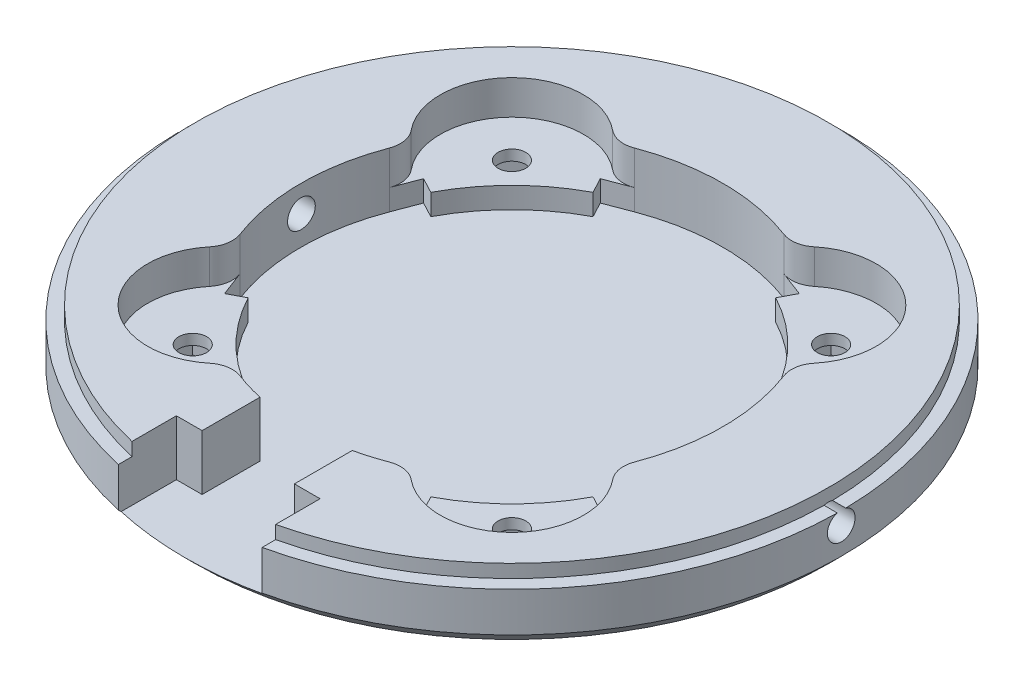
SolidWorks part; units mm, degrees
ref_plane "Front Plane" through (0, 0, 0) normal (0, 0, 1) x (1, 0, 0)
ref_plane "Top Plane" through (0, 0, 0) normal (0, 1, 0) x (1, 0, 0)
ref_plane "Right Plane" through (0, 0, 0) normal (1, 0, 0) x (0, 0, -1)
sketch "Sketch1" plane through (0, 0, 0) normal (0, 1, 0) x (1, 0, 0)
  line L0 (-15.7, 0) -> (15.7, 0) construction
  line L1 (0, 0) -> (12.1057, 12.1057) construction
  line L2 (5.6659, 14.9632) -> (7.5483, 14.2504)
  line L3 (7.5483, 14.2504) -> (6.9276, 13.0786)
  line L4 (14.9632, 5.6659) -> (14.2504, 7.5483)
  line L5 (14.2504, 7.5483) -> (13.0786, 6.9276)
  line L6 (14.9632, -5.6659) -> (14.2504, -7.5483)
  line L7 (14.2504, -7.5483) -> (13.0786, -6.9276)
  line L8 (7.5483, -14.2504) -> (6.9276, -13.0786)
  line L9 (5.6659, -14.9632) -> (7.5483, -14.2504)
  line L10 (-5.6659, -14.9632) -> (-7.5483, -14.2504)
  line L11 (-7.5483, -14.2504) -> (-6.9276, -13.0786)
  line L12 (-14.2504, -7.5483) -> (-13.0786, -6.9276)
  line L13 (-14.9632, -5.6659) -> (-14.2504, -7.5483)
  line L14 (-14.9632, 5.6659) -> (-14.2504, 7.5483)
  line L15 (-14.2504, 7.5483) -> (-13.0786, 6.9276)
  line L16 (-7.5483, 14.2504) -> (-6.9276, 13.0786)
  line L17 (-5.6659, 14.9632) -> (-7.5483, 14.2504)
  circle A0 centre (0, 0) radius 25
  circle A1 centre (0, 0) radius 15.7 construction
  circle A3 centre (12.1057, 12.1057) radius 1.05
  circle A4 centre (11.1016, 11.1016) radius 5.13 construction
  circle A5 centre (11.1016, -11.1016) radius 5.13 construction
  circle A6 centre (12.1057, -12.1057) radius 1.05
  circle A7 centre (-11.1016, -11.1016) radius 5.13 construction
  circle A8 centre (-12.1057, -12.1057) radius 1.05
  circle A9 centre (-11.1016, 11.1016) radius 5.13 construction
  circle A10 centre (-12.1057, 12.1057) radius 1.05
  arc A11 (-7.6467, 15.2907) -> (-15.2907, 7.6467) centre (-11.1016, 11.1016) ccw
  arc A12 (-14.9632, 5.6659) -> (-14.9632, -5.6659) centre (0, 0) ccw
  arc A13 (15.2907, 7.6467) -> (7.6467, 15.2907) centre (11.1016, 11.1016) ccw
  arc A14 (7.6467, -15.2907) -> (15.2907, -7.6467) centre (11.1016, -11.1016) ccw
  arc A15 (-15.2907, -7.6467) -> (-7.6467, -15.2907) centre (-11.1016, -11.1016) ccw
  circle A16 centre (-11.1016, 11.1016) radius 5.43 construction
  circle A17 centre (0, 0) radius 16 construction
  circle A18 centre (11.1016, 11.1016) radius 5.43 construction
  arc A19 (5.6659, 14.9632) -> (-5.6659, 14.9632) centre (0, 0) ccw
  circle A20 centre (-11.1016, -11.1016) radius 5.43 construction
  arc A21 (-5.6659, -14.9632) -> (5.6659, -14.9632) centre (0, 0) ccw
  circle A22 centre (11.1016, -11.1016) radius 5.43 construction
  arc A23 (14.9632, -5.6659) -> (14.9632, 5.6659) centre (0, 0) ccw
  arc A24 (5.6659, 14.9632) -> (7.6467, 15.2907) centre (6.3741, 16.8336) ccw
  arc A25 (14.9632, 5.6659) -> (15.2907, 7.6467) centre (16.8336, 6.3741) cw
  arc A26 (15.2907, -7.6467) -> (14.9632, -5.6659) centre (16.8336, -6.3741) cw
  arc A27 (-7.6467, 15.2907) -> (-5.6659, 14.9632) centre (-6.3741, 16.8336) ccw
  arc A28 (-14.9632, 5.6659) -> (-15.2907, 7.6467) centre (-16.8336, 6.3741) ccw
  arc A29 (-15.2907, -7.6467) -> (-14.9632, -5.6659) centre (-16.8336, -6.3741) ccw
  arc A30 (7.6467, -15.2907) -> (5.6659, -14.9632) centre (6.3741, -16.8336) ccw
  arc A31 (-5.6659, -14.9632) -> (-7.6467, -15.2907) centre (-6.3741, -16.8336) ccw
  circle A32 centre (0, 0) radius 14.5 construction
  arc A33 (6.9276, 13.0786) -> (13.0786, 6.9276) centre (0, 0) cw
  arc A34 (13.0786, -6.9276) -> (6.9276, -13.0786) centre (0, 0) cw
  arc A35 (-6.9276, -13.0786) -> (-13.0786, -6.9276) centre (0, 0) cw
  arc A36 (-13.0786, 6.9276) -> (-6.9276, 13.0786) centre (0, 0) cw
  arc A37 (5.6659, 14.9632) -> (-5.6659, 14.9632) centre (0, 0) ccw
  arc A38 (14.9632, 5.6659) -> (14.9632, -5.6659) centre (0, 0) cw
  arc A39 (5.6659, -14.9632) -> (-5.6659, -14.9632) centre (0, 0) cw
  arc A40 (-14.9632, -5.6659) -> (-14.9632, 5.6659) centre (0, 0) cw
  point P25 (0, 0)
  dimension "D2" = 31.4
  dimension "D3" = 50
  dimension "D4" = 2.1
  dimension "D6" = 10.26
  dimension "D9" = 2
  dimension "D10" = 29
  dimension "D11" = 14.8
  dimension "D1" = 45
  dimension "D5" = 17.12
  dimension "D12" = 0.4
  dimension "D8" = 0.3
  dimension "D7" = 4
extrude "Boss-Extrude1" add sketch "Sketch1" along normal blind 5 contours A0
extrude "Cut-Extrude1" cut sketch "Sketch1<4>" against normal blind 2.6 from surface contours A12 A29 A15 A31 A21 A30 A14 A26 A23 A25 A13 A24 A19 A27 A11 A28 starting at face at (0, 5, 25)
sketch "Sketch1<4>" plane through (0, 0, 0) normal (0, 1, 0) x (1, 0, 0) same geometry as "Sketch1"
extrude "Cut-Extrude2" cut sketch "Sketch1<5>" along normal through all contours A10 | A3 | A6 | A8
sketch "Sketch1<5>" plane through (0, 0, 0) normal (0, 1, 0) x (1, 0, 0) same geometry as "Sketch1"
sketch "Sketch3" plane through (0, 2.4, 0) normal (0, 1, 0) x (1, 0, 0)
  line L0 (5.6659, 14.9632) -> (7.5483, 14.2504) construction
  line L1 (7.5483, 14.2504) -> (6.9276, 13.0786) construction
  line L2 (14.2504, 7.5483) -> (13.0786, 6.9276) construction
  line L3 (14.9632, 5.6659) -> (14.2504, 7.5483) construction
  line L4 (14.9632, -5.6659) -> (14.2504, -7.5483) construction
  line L5 (14.2504, -7.5483) -> (13.0786, -6.9276) construction
  line L6 (7.5483, -14.2504) -> (6.9276, -13.0786) construction
  line L7 (5.6659, -14.9632) -> (7.5483, -14.2504) construction
  line L8 (-14.9632, 5.6659) -> (-14.2504, 7.5483) construction
  line L9 (-14.2504, 7.5483) -> (-13.0786, 6.9276) construction
  line L10 (-7.5483, 14.2504) -> (-6.9276, 13.0786) construction
  line L11 (-5.6659, 14.9632) -> (-7.5483, 14.2504) construction
  line L12 (-5.6659, -14.9632) -> (-7.5483, -14.2504) construction
  line L13 (-7.5483, -14.2504) -> (-6.9276, -13.0786) construction
  line L14 (-14.2504, -7.5483) -> (-13.0786, -6.9276) construction
  line L15 (-14.9632, -5.6659) -> (-14.2504, -7.5483) construction
  line L16 (5.6659, 14.9632) -> (7.5483, 14.2504)
  line L17 (7.5483, 14.2504) -> (6.9276, 13.0786)
  line L18 (14.2504, 7.5483) -> (13.0786, 6.9276)
  line L19 (14.9632, 5.6659) -> (14.2504, 7.5483)
  line L20 (14.9632, -5.6659) -> (14.2504, -7.5483)
  line L21 (14.2504, -7.5483) -> (13.0786, -6.9276)
  line L22 (7.5483, -14.2504) -> (6.9276, -13.0786)
  line L23 (5.6659, -14.9632) -> (7.5483, -14.2504)
  line L24 (-14.9632, 5.6659) -> (-14.2504, 7.5483)
  line L25 (-14.2504, 7.5483) -> (-13.0786, 6.9276)
  line L26 (-7.5483, 14.2504) -> (-6.9276, 13.0786)
  line L27 (-5.6659, 14.9632) -> (-7.5483, 14.2504)
  line L28 (-5.6659, -14.9632) -> (-7.5483, -14.2504)
  line L29 (-7.5483, -14.2504) -> (-6.9276, -13.0786)
  line L30 (-14.2504, -7.5483) -> (-13.0786, -6.9276)
  line L31 (-14.9632, -5.6659) -> (-14.2504, -7.5483)
  arc A0 (13.0786, 6.9276) -> (6.9276, 13.0786) centre (0, 0) ccw construction
  circle A1 centre (12.1057, -12.1057) radius 1.05
  circle A2 centre (12.1057, -12.1057) radius 1.05
  circle A3 centre (12.1057, 12.1057) radius 1.05
  circle A4 centre (12.1057, 12.1057) radius 1.05
  circle A9 centre (-12.1057, -12.1057) radius 1.05
  circle A10 centre (-12.1057, -12.1057) radius 1.05
  arc A11 (5.6659, 14.9632) -> (-5.6659, 14.9632) centre (0, 0) ccw construction
  arc A15 (-14.9632, 5.6659) -> (-14.9632, -5.6659) centre (0, 0) ccw construction
  arc A19 (5.6659, 14.9632) -> (-5.6659, 14.9632) centre (0, 0) ccw construction
  arc A20 (14.9632, -5.6659) -> (14.9632, 5.6659) centre (0, 0) ccw construction
  arc A24 (-5.6659, -14.9632) -> (5.6659, -14.9632) centre (0, 0) ccw construction
  arc A28 (14.9632, -5.6659) -> (14.9632, 5.6659) centre (0, 0) ccw construction
  arc A29 (-14.9632, 5.6659) -> (-14.9632, -5.6659) centre (0, 0) ccw construction
  arc A30 (6.9276, -13.0786) -> (13.0786, -6.9276) centre (0, 0) ccw construction
  arc A31 (-5.6659, -14.9632) -> (5.6659, -14.9632) centre (0, 0) ccw construction
  arc A32 (-6.9276, 13.0786) -> (-13.0786, 6.9276) centre (0, 0) ccw construction
  arc A33 (-13.0786, -6.9276) -> (-6.9276, -13.0786) centre (0, 0) ccw construction
  arc A34 (13.0786, 6.9276) -> (6.9276, 13.0786) centre (0, 0) ccw
  arc A35 (5.6659, 14.9632) -> (-5.6659, 14.9632) centre (0, 0) ccw
  arc A39 (-14.9632, 5.6659) -> (-14.9632, -5.6659) centre (0, 0) ccw
  arc A43 (5.6659, 14.9632) -> (-5.6659, 14.9632) centre (0, 0) ccw
  arc A44 (14.9632, -5.6659) -> (14.9632, 5.6659) centre (0, 0) ccw
  arc A48 (-5.6659, -14.9632) -> (5.6659, -14.9632) centre (0, 0) ccw
  arc A52 (14.9632, -5.6659) -> (14.9632, 5.6659) centre (0, 0) ccw
  arc A53 (-14.9632, 5.6659) -> (-14.9632, -5.6659) centre (0, 0) ccw
  arc A54 (6.9276, -13.0786) -> (13.0786, -6.9276) centre (0, 0) ccw
  arc A55 (-5.6659, -14.9632) -> (5.6659, -14.9632) centre (0, 0) ccw
  arc A56 (-6.9276, 13.0786) -> (-13.0786, 6.9276) centre (0, 0) ccw
  arc A57 (-13.0786, -6.9276) -> (-6.9276, -13.0786) centre (0, 0) ccw
  arc M13 (-5.6659, -14.9632) -> (5.6659, -14.9632) centre (0, 0) ccw
  arc M17 (14.9632, -5.6659) -> (14.9632, 5.6659) centre (0, 0) ccw
  arc M21 (5.6659, 14.9632) -> (-5.6659, 14.9632) centre (0, 0) ccw
  arc M25 (-14.9632, 5.6659) -> (-14.9632, -5.6659) centre (0, 0) ccw
  dimension "D1" = 0
  dimension "D2" = 0
  dimension "D5" = 0
extrude "Cut-Extrude4" cut sketch "Sketch3" against normal blind 1.6 contours L30 A57 L29 L28 L23 L22 A54 L21 L20 L19 L18 A34 L17 L16 L27 L26 A56 L25 L24 L31 M13 M17 M21 M25 region at (0, 2.4, 0)
sketch "Sketch4" plane through (0, 0, 0) normal (0, -1, 0) x (1, 0, 0)
  line L0 (-12.1057, 12.1057) -> (0, 0) construction
  line L1 (-10.391, 13.8203) -> (-12.7333, 14.4479)
  line L2 (-12.7333, 14.4479) -> (-14.4479, 12.7333)
  line L3 (-14.4479, 12.7333) -> (-13.8203, 10.391)
  line L4 (-13.8203, 10.391) -> (-11.4781, 9.7634)
  line L5 (-11.4781, 9.7634) -> (-9.7634, 11.4781)
  line L6 (-9.7634, 11.4781) -> (-10.391, 13.8203)
  line L7 (13.8203, 10.391) -> (14.4479, 12.7333)
  line L8 (14.4479, 12.7333) -> (12.7333, 14.4479)
  line L9 (12.7333, 14.4479) -> (10.391, 13.8203)
  line L10 (10.391, 13.8203) -> (9.7634, 11.4781)
  line L11 (9.7634, 11.4781) -> (11.4781, 9.7634)
  line L12 (11.4781, 9.7634) -> (13.8203, 10.391)
  line L13 (10.391, -13.8203) -> (12.7333, -14.4479)
  line L14 (12.7333, -14.4479) -> (14.4479, -12.7333)
  line L15 (14.4479, -12.7333) -> (13.8203, -10.391)
  line L16 (13.8203, -10.391) -> (11.4781, -9.7634)
  line L17 (11.4781, -9.7634) -> (9.7634, -11.4781)
  line L18 (9.7634, -11.4781) -> (10.391, -13.8203)
  line L19 (-13.8203, -10.391) -> (-14.4479, -12.7333)
  line L20 (-14.4479, -12.7333) -> (-12.7333, -14.4479)
  line L21 (-12.7333, -14.4479) -> (-10.391, -13.8203)
  line L22 (-10.391, -13.8203) -> (-9.7634, -11.4781)
  line L23 (-9.7634, -11.4781) -> (-11.4781, -9.7634)
  line L24 (-11.4781, -9.7634) -> (-13.8203, -10.391)
  circle A0 centre (-12.1057, -12.1057) radius 1.05 construction
  circle A1 centre (12.1057, -12.1057) radius 1.05 construction
  circle A2 centre (12.1057, 12.1057) radius 1.05 construction
  circle A3 centre (-12.1057, 12.1057) radius 1.05 construction
  circle A4 centre (-12.1057, -12.1057) radius 1.05 construction
  circle A5 centre (12.1057, -12.1057) radius 1.05 construction
  circle A6 centre (12.1057, 12.1057) radius 1.05 construction
  circle A7 centre (-12.1057, 12.1057) radius 1.05 construction
  circle A8 centre (-12.1057, 12.1057) radius 2.1 construction
  circle A10 centre (12.1057, 12.1057) radius 1.05 construction
  circle A11 centre (12.1057, 12.1057) radius 2.1 construction
  circle A12 centre (12.1057, -12.1057) radius 1.05 construction
  circle A13 centre (12.1057, -12.1057) radius 2.1 construction
  circle A14 centre (-12.1057, -12.1057) radius 1.05 construction
  circle A15 centre (-12.1057, -12.1057) radius 2.1 construction
  point P21 (-10.6207, 10.6207)
  point P53 (0, 0)
  dimension "D1" = 4.2
  dimension "D2" = 4
extrude "Cut-Extrude5" cut sketch "Sketch4" against normal blind 1.6
sketch "Sketch5" plane through (0, 5, 0) normal (0, 1, 0) x (1, 0, 0)
  line L1 (-3.5, 0) -> (3.5, 0)
  line L2 (-3.5, 0) -> (-3.5, -25)
  line L3 (-3.5, -25) -> (3.5, -25)
  line L4 (3.5, 0) -> (3.5, -25)
  circle A1 centre (0, 0) radius 25 construction
  point P4 (0, 0)
  dimension "D1" = 7
extrude "Cut-Extrude6" cut sketch "Sketch5" against normal up to surface (4.2 mm away) up to face at (0, 0.8, 0)
sketch "Sketch6" plane through (0, 0.8, 0) normal (0, 1, 0) x (1, 0, 0)
  line L0 (0, 0) -> (0, -20) construction
  line L1 (-5.45, -20) -> (5.45, -20)
  line L2 (-5.45, -20) -> (-5.45, -25)
  line L3 (-5.45, -25) -> (5.45, -25)
  line L4 (5.45, -20) -> (5.45, -25)
  arc A0 (-3.5, -24.7538) -> (3.5, -24.7538) centre (0, 0) ccw construction
  dimension "D1" = 10.9
  dimension "D2" = 5
extrude "Cut-Extrude7" cut sketch "Sketch6" along normal through all
sketch "Sketch7" plane through (0, 0, 0) normal (0, 0, 1) x (1, 0, 0)
  line L0 (25, 5) -> (-25, 5) construction
  line L1 (-25, 5) -> (-25, 0) construction
  line L2 (-25, 1) -> (-24, 0)
  line L3 (-25, 0) -> (25, 0) construction
  line L4 (-24, 0) -> (-25, 0)
  line L5 (-25, 0) -> (-25, 1)
  line L6 (-25, 5) -> (-24, 5)
  line L7 (-25, 5) -> (-25, 4)
  line L8 (-25, 4) -> (-24, 4)
  line L9 (-24, 5) -> (-24, 4)
  dimension "D1" = 45
  dimension "D2" = 1
  dimension "D3" = 1
  dimension "D4" = 1
ref_axis "Axis1" through (0, 5.25, 0) along (0, -1, 0)
revolve "Cut-Revolve1" cut sketch "Sketch7" angle 360 about axis through (0, 5.25, 0) along (0, -1, 0)
sketch "Sketch8" plane through (0, 0, 0) normal (1, 0, 0) x (0, 0, -1)
  line L0 (0, 5.25) -> (0, -0.25) construction
  line L1 (16.5316, 5) -> (7.6467, 5) construction
  circle A0 centre (0, 3) radius 1.05
  dimension "D1" = 2.1
  dimension "D2" = 2
extrude "Cut-Extrude8" cut sketch "Sketch8" against normal through all both and the other way through all
